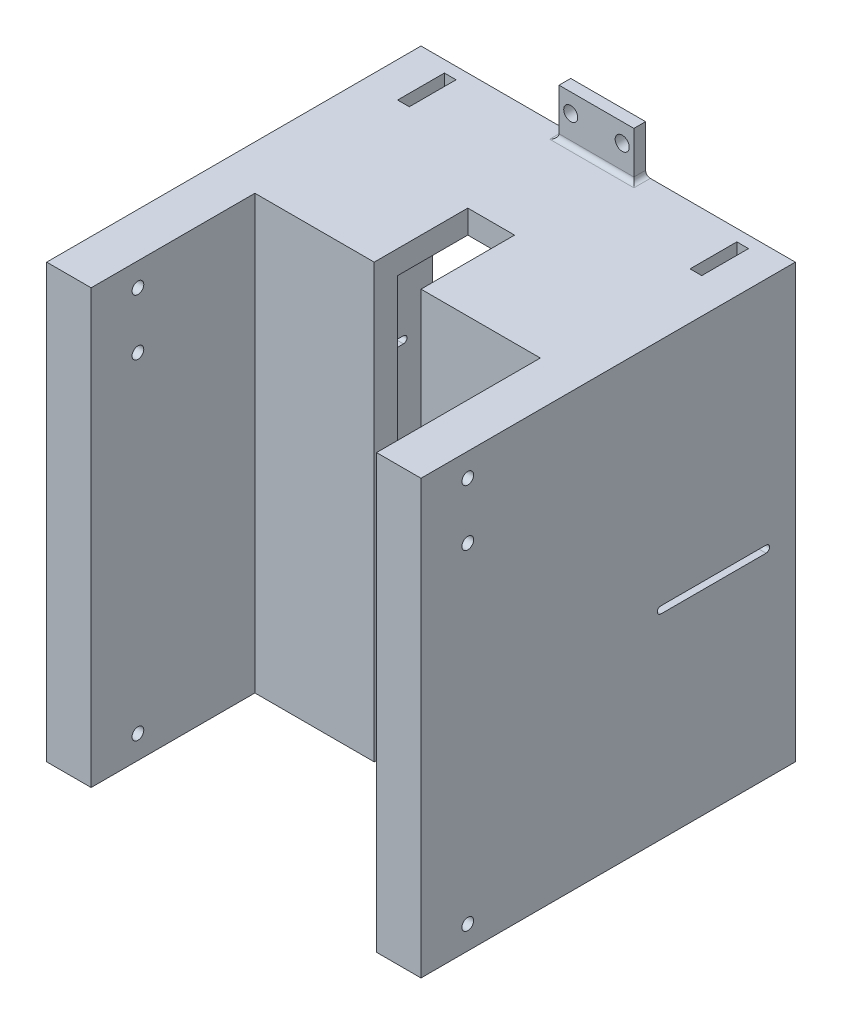
SolidWorks part; units mm, degrees
ref_plane "前基準面" through (0, 0, 0) normal (0, 0, 1) x (1, 0, 0)
ref_plane "上基準面" through (0, 0, 0) normal (0, 1, 0) x (1, 0, 0)
ref_plane "右基準面" through (0, 0, 0) normal (1, 0, 0) x (0, 0, -1)
ref_axis "基準軸1" through (0, -55, 0) along (0, 1, 0)
ref_axis "基準軸2" through (-88.99, 0, 0) along (1, 0, 0)
ref_axis "基準軸3" through (0, 0, 55) along (0, 0, -1)
sketch "草圖1" plane through (0, 0, 0) normal (0, 0, 1) x (1, 0, 0)
  line L1 (-160, -185) -> (0, -185)
  line L2 (-160, -185) -> (-160, 0)
  line L3 (-160, 0) -> (0, 0)
  line L4 (0, -185) -> (0, 0)
  dimension "D1" = 160
  dimension "D2" = 185
extrude "填料-伸長1" add sketch "草圖1" along normal blind 10
sketch "草圖2" plane through (0, 0, 0) normal (0, 0, -1) x (-1, 0, 0)
  line L0 (160, -185) -> (0, -185) construction
  line L2 (0, 0) -> (0, -185)
  line L3 (0, -185) -> (5, -185)
  line L4 (5, -10) -> (5, -185)
  line L5 (55, 0) -> (-55, 0) construction
  line L7 (160, 0) -> (160, -185)
  line L8 (160, -185) -> (155, -185)
  line L9 (155, -10) -> (155, -185)
  line L10 (160, 0) -> (160, -185) construction
  line L11 (5, -10) -> (155, -10)
  line L12 (0, 0) -> (160, 0)
  dimension "D1" = 5
  dimension "D2" = 5
  dimension "D3" = 10
extrude "填料-伸長2" add sketch "草圖2" along normal blind 80
sketch "草圖14" plane through (0, 0, 0) normal (0, 1, 0) x (1, 0, 0)
  line L0 (-80, -10) -> (-80, 74.8376) construction
  line L1 (0, -10) -> (-160, -10) construction
  line L4 (-70, -20) -> (-70, 30)
  line L5 (-70, 30) -> (-90, 30)
  line L6 (-90, -20) -> (-90, 30)
  line L10 (-90, -20) -> (-70, -20)
  point P8 (-80, 30)
  dimension "D1" = 10
  dimension "D2" = 40
  dimension "D3" = 20
extrude "除料-伸長4" cut sketch "草圖14" against normal through all
sketch "草圖16" plane through (0, 0, -80) normal (0, 0, -1) x (-1, 0, 0)
  line L0 (160, 0) -> (0, 0) construction
  line L1 (96, 0) -> (64, 0)
  line L2 (96, 0) -> (96, -10) construction
  line L3 (96, -10) -> (64, -10) construction
  line L4 (64, 0) -> (64, -10) construction
  line L5 (90, -10) -> (155, -10) construction
  line L6 (80, 0) -> (80, -74.9509) construction
  line L7 (64, 0) -> (64, 20)
  line L8 (64, 20) -> (96, 20)
  line L9 (96, 20) -> (96, 0)
  dimension "D1" = 20
  dimension "D2" = 32
extrude "填料-伸長7" add sketch "草圖16" against normal blind 5
sketch "草圖18" plane through (0, 0, -80) normal (0, 0, -1) x (-1, 0, 0)
  line L0 (80, 20) -> (80, -10) construction
  line L1 (96, 20) -> (64, 20) construction
  line L2 (5, -10) -> (155, -10) construction
  line L3 (64, 4) -> (96, 4) construction
  line L4 (64, 20) -> (64, 0) construction
  line L5 (96, 0) -> (96, 20) construction
  line L6 (69, 12) -> (91, 12) construction
  circle A0 centre (69, 12) radius 3
  circle A1 centre (91, 12) radius 3
  point P15 (80, 12)
  dimension "D4" = 6
  dimension "D1" = 16
  dimension "D2" = 11
  dimension "D3" = 8
extrude "除料-伸長7" cut sketch "草圖18" against normal up to next
fillet "圓角1" radius 2 3 edges at (-64, 0, -77.5) (-80, 0, -75) (-96, 0, -77.5)
sketch "草圖21" plane through (-160, 0, 0) normal (-1, 0, 0) x (0, 0, 1)
  line L11 (10, 0) -> (80, 0)
  line L12 (80, 0) -> (80, -185)
  line L13 (80, -185) -> (10, -185)
  line L14 (10, 0) -> (10, -185) construction
  line L15 (10, 0) -> (10, -185)
  circle A1 centre (60, -10) radius 2.5
  circle A2 centre (60, -175) radius 2.5
  circle A3 centre (60, -34) radius 2.5
  dimension "D5" = 70
  dimension "D3" = 10
  dimension "D4" = 5
  dimension "D6" = 24
  dimension "D7" = 5
  dimension "D1" = 10
  dimension "D2" = 50
extrude "填料-伸長8" add sketch "草圖21" against normal up to surface (160 mm away) up to face at (0, -92.5, -35)
sketch "草圖22" plane through (-155, 0, 0) normal (1, 0, 0) x (0, 0, -1)
  line L0 (0, -100) -> (75.9887, -100) construction
  line L1 (22.5, -100) -> (67.5, -100) construction
  line L2 (22.5, -98.5) -> (67.5, -98.5)
  line L3 (22.5, -101.5) -> (67.5, -101.5)
  line L4 (0, -10) -> (0, -185)
  line L5 (0, -185) -> (80, -185)
  line L6 (80, -185) -> (80, -10)
  line L7 (80, -10) -> (0, -10)
  line L8 (0, -10) -> (0, -185) construction
  line L9 (0, -185) -> (80, -185) construction
  line L10 (80, -185) -> (80, -10) construction
  line L11 (80, -10) -> (0, -10) construction
  line L12 (80, -185) -> (80, 0) construction
  arc A0 (22.5, -98.5) -> (22.5, -101.5) centre (22.5, -100) ccw
  arc A1 (67.5, -101.5) -> (67.5, -98.5) centre (67.5, -100) ccw
  point P8 (45, -100)
  point P13 (0, 0)
  point P14 (0, 0)
  point P15 (75.9887, -97.5)
  point P16 (0, 0)
  point P17 (0, 0)
  point P18 (0, 0)
  dimension "D3" = 3
  dimension "D2" = 45
  dimension "D4" = 12.5
  dimension "D5" = 90
  dimension "D1" = 0
extrude "除料-伸長9" cut sketch "草圖22" against normal through all both and the other way through all contours L3 A1 L2 A0
sketch "草圖23" plane through (0, 0, 0) normal (0, 1, 0) x (1, 0, 0)
  line L0 (0, -80) -> (-160, -80) construction
  line L1 (-19, -80) -> (-141, -80)
  line L2 (-19, -80) -> (-19, -10)
  line L3 (-19, -10) -> (-141, -10)
  line L4 (-141, -80) -> (-141, -10)
  line L5 (-160, -80) -> (-160, 80) construction
  line L6 (-70, -10) -> (-90, -10) construction
  line L7 (0, -80) -> (0, 80) construction
  dimension "D1" = 19
  dimension "D2" = 19
extrude "除料-伸長10" cut sketch "草圖23" against normal through all
sketch "草圖24" plane through (0, 0, 0) normal (0, 1, 0) x (1, 0, 0)
  line L0 (-80, 80) -> (-80, -45.9298) construction
  line L1 (-145, 75) -> (-140, 75)
  line L2 (-145, 75) -> (-145, 55)
  line L3 (-145, 55) -> (-140, 55)
  line L4 (-140, 75) -> (-140, 55)
  line L5 (-20, 75) -> (-15, 75)
  line L6 (-20, 75) -> (-20, 55)
  line L7 (-20, 55) -> (-15, 55)
  line L8 (-15, 75) -> (-15, 55)
  line L9 (-96, 80) -> (-64, 80) construction
  line L10 (-160, 80) -> (-98, 80) construction
  point P12 (-142.5, 75)
  dimension "D1" = 15
  dimension "D2" = 5
  dimension "D3" = 20
  dimension "D4" = 5
extrude "除料-伸長11" cut sketch "草圖24" against normal up to next
